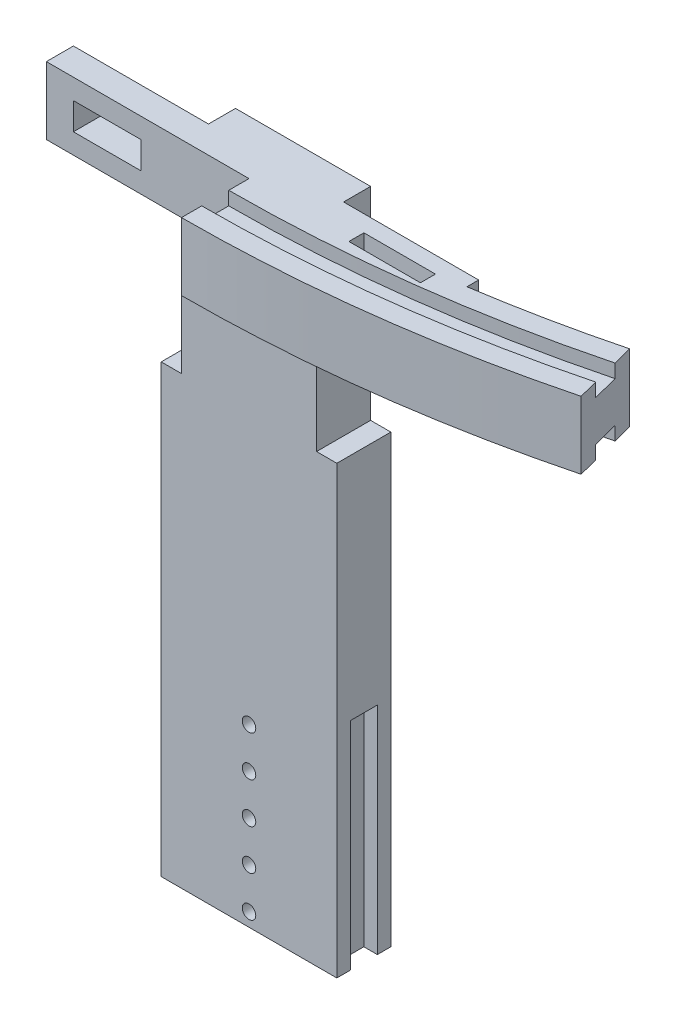
SolidWorks part; units mm, degrees
ref_plane "Front Plane" through (0, 0, 0) normal (0, 0, 1) x (1, 0, 0)
ref_plane "Top Plane" through (0, 0, 0) normal (0, 1, 0) x (1, 0, 0)
ref_plane "Right Plane" through (0, 0, 0) normal (1, 0, 0) x (0, 0, -1)
sketch "Sketch1" plane through (0, 0, 0) normal (0, 1, 0) x (1, 0, 0)
  line L0 (0, 23.6458) -> (0, -25.0113) construction
  line L1 (65, 20) -> (-65, 20)
  line L2 (-65, 20) -> (-65, 10)
  line L3 (-65, 10) -> (-55, 10)
  line L4 (-55, 10) -> (-55, -10)
  line L5 (-55, -10) -> (-65, -10)
  line L6 (-65, -10) -> (-65, -20)
  line L7 (-65, -20) -> (65, -20)
  line L8 (-55, 0) -> (55, 0) construction
  line L9 (65, -10) -> (65, -20)
  line L10 (55, -10) -> (65, -10)
  line L11 (55, 10) -> (55, -10)
  line L12 (65, 10) -> (55, 10)
  line L13 (65, 20) -> (65, 10)
  point P13 (-4.7118, -0.7765)
  point P14 (0, -1.7765)
  point P15 (0, 23.6458)
  point P16 (0, -25.0113)
  point P18 (0, -20)
  point P23 (0, 20)
  dimension "D1" = 10
  dimension "D2" = 40
  dimension "D3" = 10
  dimension "D4" = 130
extrude "body" add sketch "Sketch1" along normal blind 160
sketch "Sketch2" plane through (0, 0, 20) normal (0, 0, 1) x (1, 0, 0)
  line L0 (0, 0) -> (0, 160) construction
  line L1 (-65, 160) -> (65, 160) construction
  circle A0 centre (0, 10) radius 5
  point P7 (0, 0)
  point P8 (0, 0)
  dimension "D1" = 10
  dimension "D2" = 10
extrude "pin hole" cut sketch "Sketch2" against normal through all
pattern_linear "LPattern1" count 5 spacing 30 along (0, 1, 0) of "pin hole"
sketch "Sketch3" plane through (0, 0, 20) normal (0, 0, 1) x (1, 0, 0)
  line L1 (-65, 160) -> (65, 160)
  line L2 (-65, 160) -> (-65, 330)
  line L3 (-65, 330) -> (65, 330)
  line L4 (65, 160) -> (65, 330)
  line L5 (-50, 330) -> (50, 330)
  line L6 (-50, 330) -> (-50, 480)
  line L7 (-50, 480) -> (50, 480)
  line L8 (50, 330) -> (50, 480)
  point P4 (0, 330)
  point P11 (0, 160)
  point P12 (0, 330)
  line M13 (65, 160) -> (-65, 160)
  dimension "D1" = 170
  dimension "D2" = 150
  dimension "D3" = 100
extrude "spine" add sketch "Sketch3" against normal up to surface (40 mm away) contours L4 L3 L2 M13 | L3 L8 L7 L6 region at (0, 245, 20) region at (0, 405, 20) up to face at (5, 40, -20)
sketch "Sketch6" plane through (0, 0, 0) normal (1, 0, 0) x (0, 0, -1)
  line L0 (-20, 330) -> (-20, 480) construction
  line L1 (-70, 480) -> (-55, 480)
  line L2 (-70, 480) -> (-70, 430)
  line L3 (-70, 430) -> (-55, 430)
  line L4 (-20, 480) -> (-20, 430)
  line L5 (-35, 480) -> (-20, 480)
  line L6 (-35, 430) -> (-20, 430)
  line L8 (-55, 480) -> (-55, 470)
  line L9 (-55, 470) -> (-35, 470)
  line L10 (-35, 480) -> (-35, 470)
  line L12 (-55, 430) -> (-55, 440)
  line L13 (-55, 440) -> (-35, 440)
  line L14 (-35, 430) -> (-35, 440)
  point P6 (0, 0)
  point P16 (0, 0)
  point P17 (-56.7647, 441.9905)
  point P21 (0, 0)
  dimension "D1" = 50
  dimension "D2" = 50
  dimension "D3" = 15
  dimension "D4" = 10
  dimension "D5" = 20
  dimension "D6" = 10
extrude "slider" [suppressed] add sketch "Sketch6" along normal blind 150 contours L14 L3 L4 L1 L10 L9 L8 L2 L12 L13
sketch "Sketch8" plane through (0, 480, 0) normal (0, 1, 0) x (1, 0, 0)
  line L0 (-50, -20) -> (50, -20) construction
  line L1 (0, -20) -> (0, 20) construction
  line L2 (50, 20) -> (-50, 20) construction
  line L3 (250, -20) -> (250, 20) construction
  arc A0 (0, -20) -> (250, 11.7542) centre (0, 980) ccw
  dimension "D1" = 2000
  dimension "D2" = 250
sweep "Sweep4" add profiles "Sketch6<6>" path "Sketch8"
sketch "Sketch6<6>" plane through (0, 0, 0) normal (1, 0, 0) x (0, 0, -1) same geometry as "Sketch6"
sketch "Sketch9" plane through (0, 480, 0) normal (0, 1, 0) x (1, 0, 0)
  line L1 (0, 110.1428) -> (200, 110.1428)
  line L2 (0, 110.1428) -> (0, -182.1774)
  line L3 (0, -182.1774) -> (200, -182.1774)
  line L4 (200, 110.1428) -> (200, -182.1774)
  point P4 (100, 110.1428)
  dimension "D1" = 292.3202
  dimension "D2" = 200
sketch "Sketch10" plane through (0, 0, 20) normal (0, 0, 1) x (1, 0, 0)
  line L0 (0, 430) -> (262.5, 430) construction
  line L1 (-150, 480) -> (150, 480)
  line L2 (-150, 480) -> (-150, 430)
  line L3 (-150, 430) -> (150, 430)
  line L4 (150, 480) -> (150, 430)
  line L5 (0, 480) -> (0, 430) construction
  line L6 (-130, 465) -> (-80, 465)
  line L7 (-130, 465) -> (-130, 445)
  line L8 (-130, 445) -> (-80, 445)
  line L9 (-80, 465) -> (-80, 445)
  line L10 (130, 445) -> (80, 445)
  line L11 (130, 465) -> (130, 445)
  line L12 (130, 465) -> (80, 465)
  line L13 (80, 465) -> (80, 445)
  point P7 (0, 480)
  dimension "D1" = 50
  dimension "D2" = 300
  dimension "D3" = 20
  dimension "D4" = 50
  dimension "D5" = 20
  dimension "D6" = 15
extrude "Boss-Extrude5" add sketch "Sketch10" against normal blind 20
sketch "Sketch11" plane through (0, 480, 0) normal (0, 1, 0) x (1, 0, 0)
  line L1 (77.2883, -12.2284) -> (130.2304, -12.2284)
  line L2 (77.2883, -12.2284) -> (77.2883, -23.3455)
  line L3 (77.2883, -23.3455) -> (130.2304, -23.3455)
  line L4 (130.2304, -12.2284) -> (130.2304, -23.3455)
  dimension "D1" = 11.1171
  dimension "D2" = 52.9421
extrude "Cut-Extrude2" cut sketch "Sketch11" against normal up to next
